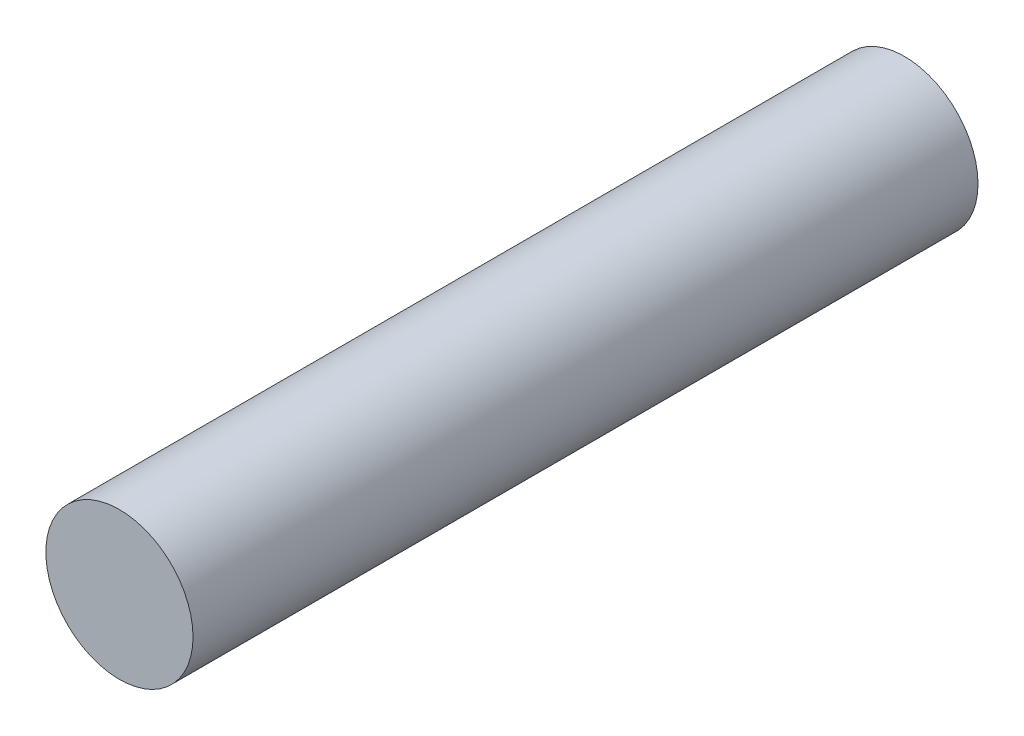
SolidWorks part; units mm, degrees
material "3.0255 (EN-AW 1350A)"
ref_plane "정면" through (0, 0, 0) normal (0, 0, 1) x (1, 0, 0)
ref_plane "윗면" through (0, 0, 0) normal (0, 1, 0) x (1, 0, 0)
ref_plane "우측면" through (0, 0, 0) normal (1, 0, 0) x (0, 0, -1)
sketch "스케치2" plane through (0, 0, 0) normal (0, 0, 1) x (1, 0, 0)
  circle A0 centre (0, 0) radius 4
  circle A1 centre (0, 0) radius 7.5
  dimension "D1" = 8
  dimension "D2" = 15
extrude "보스-돌출1" add sketch "스케치2" along normal blind 80 contours A1
extrude "컷-돌출1" cut sketch "스케치2<3>" along normal blind 30 contours A0 region at (0, 0, 0)
sketch "스케치2<3>" plane through (0, 0, 0) normal (0, 0, 1) x (1, 0, 0) same geometry as "스케치2"
sketch "스케치3" plane through (0, 0, 0) normal (0, 1, 0) x (1, 0, 0)
  line L1 (7.5, 0) -> (-7.5, 0) construction
  line L2 (-7.5, -80) -> (7.5, -80) construction
  circle A0 centre (0, -25) radius 2
  circle A1 centre (0, -75) radius 2
  point P9 (0, 0)
  dimension "D2" = 4
  dimension "D3" = 4
  dimension "D1" = 25
  dimension "D4" = 5
extrude "컷-돌출2" cut sketch "스케치3" against normal blind 10
